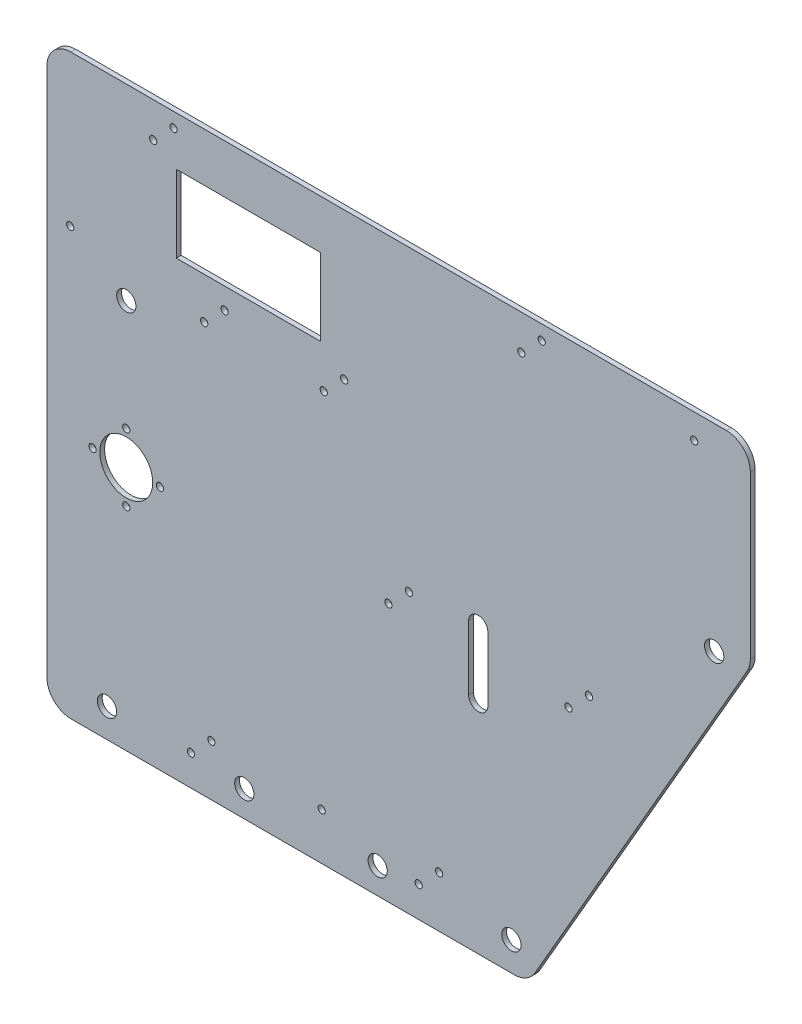
SolidWorks part; units mm, degrees
ref_plane "Front Plane" through (0, 0, 0) normal (0, 0, 1) x (1, 0, 0)
ref_plane "Top Plane" through (0, 0, 0) normal (0, 1, 0) x (1, 0, 0)
ref_plane "Right Plane" through (0, 0, 0) normal (1, 0, 0) x (0, 0, -1)
sketch "Sketch1" plane through (0, 0, 0) normal (0, 0, 1) x (1, 0, 0)
  line L0 (100, 80) -> (192.376, 80)
  line L1 (-100, -80) -> (100, -80)
  line L2 (-100, -80) -> (-100, 80)
  line L3 (-100, 80) -> (100, 80)
  line L4 (100, -80) -> (100, 80)
  line L5 (-100, -80) -> (100, 80) construction
  line L6 (-100, 80) -> (100, -80) construction
  line L7 (192.376, 80) -> (100, -80)
  line L8 (100, 80) -> (100, -80)
  line L10 (-100, 80) -> (192.376, 80)
  line L11 (-100, 80) -> (-100, 110)
  line L12 (-100, 110) -> (192.376, 110)
  line L13 (192.376, 80) -> (192.376, 110)
  point P0 (0, 0)
  dimension "D1" = 160
  dimension "D2" = 200
  dimension "D3" = 30
  dimension "D4" = 30
extrude "Boss-Extrude1" add sketch "Sketch1" along normal blind 2 contours L1 L4 L3 L2 | L7 L0 L4 | L11 L10 L13 L12 region at (0, 0, 0) region at (130.792, 26.6667, 0)
sketch "Sketch2" plane through (0, 0, 2) normal (0, 0, 1) x (1, 0, 0)
  line L0 (-100, -80) -> (100, -80) construction
  line L1 (192.376, 80) -> (100, -80) construction
  line L2 (79.2904, 11.2418) -> (79.2904, 37.9086) construction
  line L3 (-100, -80) -> (-100, 110) construction
  line L4 (-100, 110) -> (192.376, 110) construction
  line L7 (-100, 110) -> (192.376, 110) construction
  line L8 (75.2904, 11.2418) -> (75.2904, 37.9086)
  line L11 (-100, -80) -> (-100, 110) construction
  line L12 (83.2904, 11.2418) -> (83.2904, 37.9086)
  line L13 (-100, -80) -> (-100, 110) construction
  line L14 (-67, 22) -> (-67, 85.6687) construction
  circle A0 centre (93.0718, -68) radius 4
  circle A1 centre (177.3649, 78) radius 4
  circle A2 centre (-67, 22) radius 11
  circle A3 centre (-75, -68) radius 4
  circle A4 centre (-53, 22) radius 1.5
  circle A5 centre (-67, 36) radius 1.5
  circle A6 centre (-81, 22) radius 1.5
  circle A7 centre (-67, 8) radius 1.5
  circle A11 centre (54.5495, -67.2426) radius 1.5
  circle A12 centre (63.0348, -58.7574) radius 1.5
  circle A13 centre (14.2259, -60.5) radius 1.5
  circle A14 centre (-40.1271, -67.2426) radius 1.5
  circle A15 centre (-31.6419, -58.7574) radius 1.5
  circle A16 centre (-90.2956, 97.2169) radius 1.5
  circle A17 centre (-34.6051, 90.4743) radius 1.5
  circle A18 centre (-26.1198, 98.9596) radius 1.5
  circle A19 centre (15.0782, 90.4743) radius 1.5
  circle A20 centre (23.5635, 98.9596) radius 1.5
  circle A21 centre (41.9695, 27.4743) radius 1.5
  circle A22 centre (50.4548, 35.9596) radius 1.5
  circle A23 centre (-39.813, 27.4743) radius 1.5 construction
  circle A24 centre (-31.3277, 35.9596) radius 1.5 construction
  circle A25 centre (116.8113, 27.4743) radius 1.5
  circle A26 centre (125.2966, 35.9596) radius 1.5
  circle A27 centre (79.2904, 25) radius 4 construction
  circle A31 centre (169.0558, 149.7306) radius 1.5
  arc A32 (75.2904, 11.2418) -> (83.2904, 11.2418) centre (79.2904, 11.2418) ccw
  arc A33 (83.2904, 37.9086) -> (75.2904, 37.9086) centre (79.2904, 37.9086) ccw
  circle A34 centre (-55.8147, 145.4743) radius 1.5
  circle A35 centre (-47.3294, 153.9596) radius 1.5
  circle A36 centre (97.1924, 145.4743) radius 1.5
  circle A37 centre (105.6777, 153.9596) radius 1.5
  circle A38 centre (-17.9479, -69.1174) radius 4
  circle A39 centre (37.4944, -69.1174) radius 4
  circle A40 centre (-67, 22) radius 40 construction
  circle A41 centre (-67, 82) radius 20 construction
  circle A42 centre (-67, 82) radius 4
  point P87 (79.2904, 24.5752)
  dimension "D3" = 8
  dimension "D4" = 8
  dimension "D9" = 22
  dimension "D10" = 8
  dimension "D12" = 3
  dimension "D13" = 3
  dimension "D14" = 3
  dimension "D15" = 3
  dimension "D16" = 14
  dimension "D20" = 13.3334
  dimension "D22" = 179.2904
  dimension "D25" = 3
  dimension "D26" = 3
  dimension "D29" = 8
  dimension "D28" = 3
  dimension "D31" = 8
  dimension "D32" = 8
  dimension "D23" = 12.9086
  dimension "D24" = 80
  dimension "D34" = 40
  dimension "D35" = 8
  dimension "D1" = 12
  dimension "D2" = 12
  dimension "D5" = 32
  dimension "D6" = 12
  dimension "D7" = 88
  dimension "D8" = 33
  dimension "D11" = 12
  dimension "D17" = 14
  dimension "D18" = 14
  dimension "D19" = 14
  dimension "D21" = 85.4248
  dimension "D27" = 25
  dimension "D30" = 8
  dimension "D33" = 60
extrude "Cut-Extrude1" cut sketch "Sketch2" against normal blind 3
sketch "Sketch4" plane through (0, 0, 2) normal (0, 0, 1) x (1, 0, 0)
  line L0 (192.376, 80) -> (192.376, 110) construction
  line L1 (-100, 110) -> (192.376, 110)
  line L2 (-100, 110) -> (-100, 160)
  line L3 (-100, 160) -> (192.376, 160)
  line L4 (192.376, 110) -> (192.376, 160)
  dimension "D1" = 50
extrude "Boss-Extrude2" add sketch "Sketch4" against normal blind 2
fillet "Fillet1" radius 10 5 edges at (192.376, 160, 1) (192.376, 80, 1) (100, -80, 1) (-100, -80, 1) (-100, 160, 1)
sketch "Sketch5" plane through (0, 0, 2) normal (0, 0, 1) x (1, 0, 0)
  line L1 (-46.1781, 107.7169) -> (13.8219, 107.7169)
  line L2 (-46.1781, 107.7169) -> (-46.1781, 139.7169)
  line L3 (-46.1781, 139.7169) -> (13.8219, 139.7169)
  line L4 (13.8219, 107.7169) -> (13.8219, 139.7169)
  circle A2 centre (-55.8147, 145.4743) radius 1.5
  circle A3 centre (-47.3294, 153.9596) radius 1.5
  circle A4 centre (97.1924, 145.4743) radius 1.5
  circle A5 centre (105.6777, 153.9596) radius 1.5
  circle A6 centre (169.0558, 149.7306) radius 1.5
  dimension "D1" = 3
extrude "Cut-Extrude2" cut sketch "Sketch5" against normal blind 11
